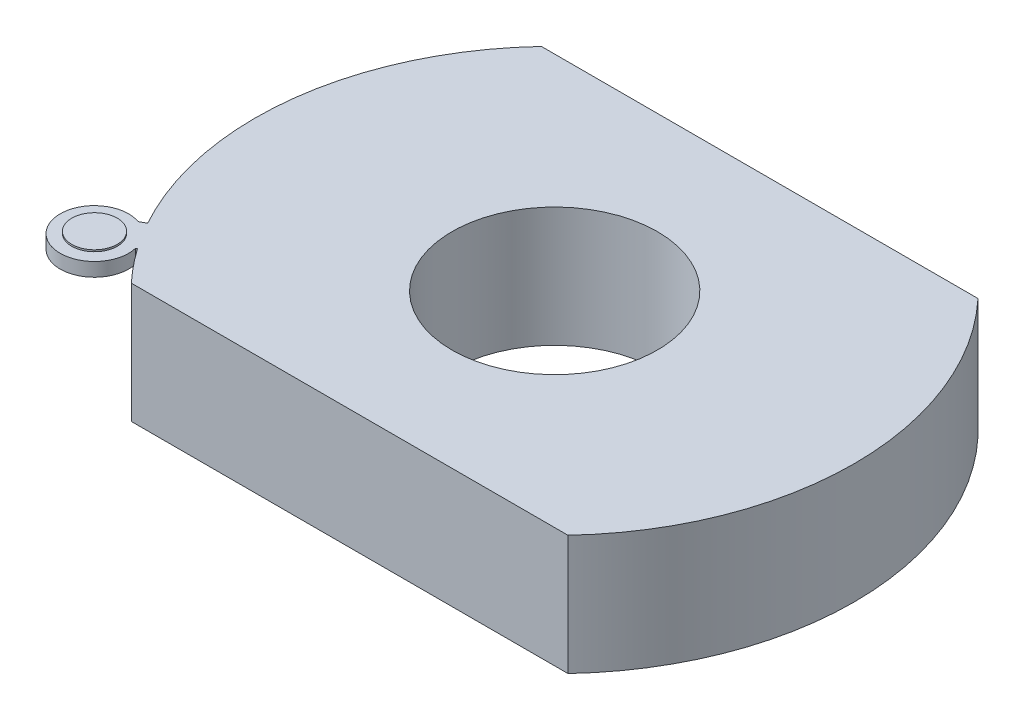
SolidWorks part; units mm, degrees
material "1345 Alloy"
ref_plane "Front Plane" through (0, 0, 0) normal (0, 0, 1) x (1, 0, 0)
ref_plane "Top Plane" through (0, 0, 0) normal (0, 1, 0) x (1, 0, 0)
ref_plane "Right Plane" through (0, 0, 0) normal (1, 0, 0) x (0, 0, -1)
sketch "Sketch1" plane through (0, 0, 0) normal (0, 1, 0) x (1, 0, 0)
  line L0 (-1712.4333, 578.2677) -> (-1658.0172, 559.892) construction
  line L1 (-1682.6566, 611.2885) -> (-1644.8226, 597.5438) construction
  line L2 (-1769.951, 660.0706) -> (-1712.4333, 741.8735) construction
  circle A0 centre (0, 0) radius 1750
  arc A3 (-1712.4333, 578.2677) -> (-1712.4333, 741.8735) centre (-1769.951, 660.0706) cw construction
  arc A4 (-1712.4333, 741.8735) -> (-1682.6566, 611.2885) centre (-1769.951, 660.0706) cw construction
extrude "Boss-Extrude1" add sketch "Sketch1" along normal blind 700
sketch "Sketch9" plane through (0, 0, 0) normal (0, -1, 0) x (1, 0, 0)
  line L1 (-2106.3119, -1198.0599) -> (2106.3119, -1198.0599)
  line L2 (-2106.3119, -1198.0599) -> (-2106.3119, 1198.0599)
  line L3 (-2106.3119, 1198.0599) -> (2106.3119, 1198.0599)
  line L4 (2106.3119, -1198.0599) -> (2106.3119, 1198.0599)
  line L5 (-2106.3119, -1198.0599) -> (2106.3119, 1198.0599) construction
  line L6 (-2106.3119, 1198.0599) -> (2106.3119, -1198.0599) construction
  line L7 (-2636.6179, -2082.9122) -> (2636.6179, -2082.9122)
  line L8 (-2636.6179, -2082.9122) -> (-2636.6179, 2082.9122)
  line L9 (-2636.6179, 2082.9122) -> (2636.6179, 2082.9122)
  line L10 (2636.6179, -2082.9122) -> (2636.6179, 2082.9122)
  line L11 (-2636.6179, -2082.9122) -> (2636.6179, 2082.9122) construction
  line L12 (-2636.6179, 2082.9122) -> (2636.6179, -2082.9122) construction
  point P0 (0, 0)
  point P6 (0, 0)
extrude "Cut-Extrude10" cut sketch "Sketch9" against normal through all both and the other way through all
sketch "Sketch3" plane through (0, 0, 0) normal (0, -1, 0) x (1, 0, 0)
  circle A0 centre (0, 0) radius 600
extrude "Cut-Extrude3" cut sketch "Sketch3" against normal through all both and the other way through all
shell "Shell1" thickness 1.5 removed face at (0, 0, 600)
sketch "Sketch12" plane through (0, 700, 0) normal (0, 1, 0) x (1, 0, 0)
  line L0 (-1432.0962, -1005.7836) -> (-1439.5944, -1011.0497)
  line L1 (-1432.0962, -1005.7836) -> (-1439.5944, -1011.0497)
  line L2 (-1567.0537, -866.7535) -> (-1531.3623, -847.0122)
  line L3 (-1212.6439, -1163.1539) -> (-1531.3623, -847.0122) construction
  line L6 (-1275.5989, 1198.0599) -> (1275.5989, -1198.0599) construction
  line L7 (0, 0) -> (-1750, 0) construction
  line L13 (0, 0) -> (0, 1750) construction
  line L14 (1212.6439, 1163.1539) -> (1394.7434, 1056.9725) construction
  line L15 (1533.0685, 1076.2848) -> (1275.8583, 1198.0599) construction
  line L16 (1432.0962, 1005.7836) -> (1533.0685, 1076.2848)
  line L17 (1432.0962, 1005.7836) -> (1533.0685, 1076.2848)
  line L18 (1456.8867, 1104.0663) -> (1394.7434, 1056.9725)
  arc A0 (-1275.5989, -1198.0599) -> (-1531.3623, -847.0122) centre (0, 0) cw
  arc A1 (-1432.0962, 1005.7836) -> (-1275.5989, 1198.0599) centre (0, 0) ccw construction
  arc A2 (-1439.5944, -1011.0497) -> (-1567.0537, -866.7535) centre (-1634.7144, -1054.9609) cw
  arc A3 (-1432.0962, -1005.7836) -> (-1275.5989, -1198.0599) centre (0, 0) cw construction
  arc A4 (1275.8583, 1198.0599) -> (1394.7434, 1056.9725) centre (24.3381, 22.854) cw
  arc A6 (1533.0685, 1076.2848) -> (1456.8867, 1104.0663) centre (1562.0755, 1274.1701) cw
  point P2 (-1620.5682, -1056.5335)
  point P13 (-1634.7144, -1054.9609)
  point P19 (-1600.5562, -1138.8314)
  point P22 (-1678.0027, -1043.7063)
  point P23 (-1667.1341, -1021.045)
  point P24 (-1549.9878, -812.4271)
  arc M6 (-1275.5989, 1198.0599) -> (-1275.5989, -1198.0599) centre (0, 0) ccw
extrude "Boss-Extrude2" add sketch "Sketch12" against normal blind 80 contours A2 L0 L2 M6 region at (-1633.7874, 700, 1053.2699)
sketch "Sketch14" plane through (0, 700, 0) normal (0, 1, 0) x (1, 0, 0)
  circle A0 centre (-1636.0595, -1052.8306) radius 132.8125
  point P0 (-1636.0595, -1052.8306)
extrude "Boss-Extrude5" add sketch "Sketch14" along normal blind 10
sketch "Sketch18" plane through (0, 698.5, 0) normal (0, -1, 0) x (1, 0, 0)
  line L0 (0, 0) -> (-1178.7098, 0) construction
  line L6 (-1278.7098, -100) -> (-1078.7098, -100)
  line L7 (-1278.7098, -100) -> (-1278.7098, 100)
  line L8 (-1278.7098, 100) -> (-1078.7098, 100)
  line L9 (-1078.7098, -100) -> (-1078.7098, 100)
  line L10 (-1278.7098, -100) -> (-1078.7098, 100) construction
  line L11 (-1278.7098, 100) -> (-1078.7098, -100) construction
  circle A0 centre (-1178.7098, 0) radius 27.5
  point P8 (-1136.0909, 0)
  point P9 (-1212.6153, 0)
  point P10 (-1147.4117, 0)
  point P11 (-1168.6683, 0)
  point P12 (-1178.7098, 0)
extrude "Boss-Extrude6" add sketch "Sketch18" along normal blind 50
